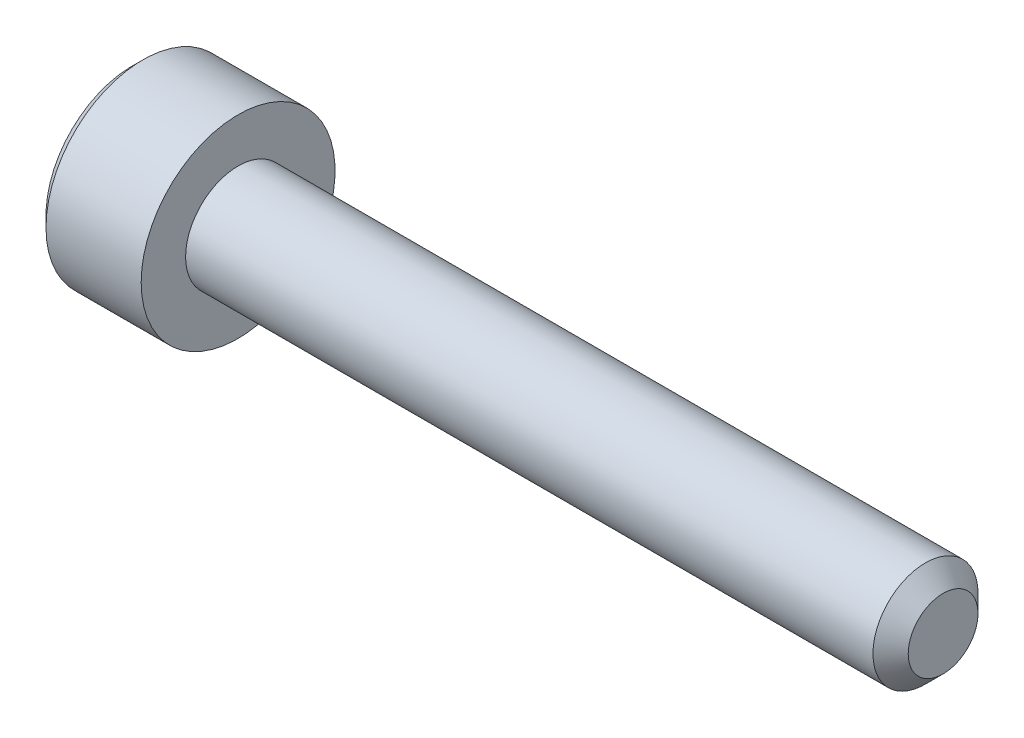
SolidWorks part; units mm, degrees
material "AISI Type 316L stainless steel"
ref_plane "Front Plane" through (0, 0, 0) normal (0, 0, 1) x (1, 0, 0)
ref_plane "Top Plane" through (0, 0, 0) normal (0, 1, 0) x (1, 0, 0)
ref_plane "Right Plane" through (0, 0, 0) normal (1, 0, 0) x (0, 0, -1)
sketch "Sketch1" plane through (0, 0, 0) normal (0, 0, 1) x (1, 0, 0)
  line L0 (-88.7055, 0) -> (96.9812, 0) construction
  line L1 (0, 0) -> (0, 2.75)
  line L2 (0, 2.75) -> (3, 2.75)
  line L4 (23, 0) -> (23, 1.49)
  line L5 (23, 1.49) -> (3, 1.49)
  line L6 (3, 1.49) -> (3, 2.75)
  line L7 (0, 0) -> (23, 0)
revolve "Revolve1" add sketch "Sketch1" angle 360 about L0
chamfer "Chamfer1" distance 0.5 angle 45 1 edges at (23, 0, 1.49)
chamfer "Chamfer2" distance 0.3 angle 45 1 edges at (0, 0, 2.75)
sketch "Sketch3" plane through (0, 0, 0) normal (1, 0, 0) x (0, 0, -1)
  line L1 (-1.4434, 0) -> (-0.7217, -1.25)
  line L2 (-0.7217, -1.25) -> (0.7217, -1.25)
  line L3 (0.7217, -1.25) -> (1.4434, 0)
  line L4 (1.4434, 0) -> (0.7217, 1.25)
  line L5 (0.7217, 1.25) -> (-0.7217, 1.25)
  line L6 (-0.7217, 1.25) -> (-1.4434, 0)
  circle A0 centre (0, 0) radius 1.25 construction
extrude "Cut-Extrude1" cut sketch "Sketch3" along normal blind 2.5
chamfer "Chamfer3" distance 0.3 angle 45 6 edges at (0, 1.25, 0) (0, 0.625, 1.0825) (0, -0.625, 1.0825) (0, -1.25, 0) (0, -0.625, -1.0825) (0, 0.625, -1.0825)
sketch "Sketch5" plane through (23, 0, 0) normal (1, 0, 0) x (0, 0, -1)
  circle A0 centre (0, 0) radius 1.49
curve "Helix/Spiral1" pitch 0.5 height 20 turns 40
sketch "Sketch8" plane through (0, 0, 0) normal (0, 1, 0) x (1, 0, 0)
  line L0 (23, 1.49) -> (23, 1.1111) construction
  line L1 (23.0625, 1.2194) -> (23.3281, 1.6794)
  line L2 (23.3281, 1.6794) -> (22.6719, 1.6794)
  line L3 (22.6719, 1.6794) -> (22.9375, 1.2194)
  line L4 (23, -0.99) -> (23, 0.99) construction
  circle A0 centre (23, 1.49) radius 0.1894 construction
  arc A1 (23.0625, 1.2194) -> (22.9375, 1.2194) centre (23, 1.2555) cw
  dimension "D2" = 0.0722
  dimension "D1" = 0.3789
sweep "Cut-Sweep1" [suppressed] cut profiles "Sketch8" path "Helix/Spiral1"
